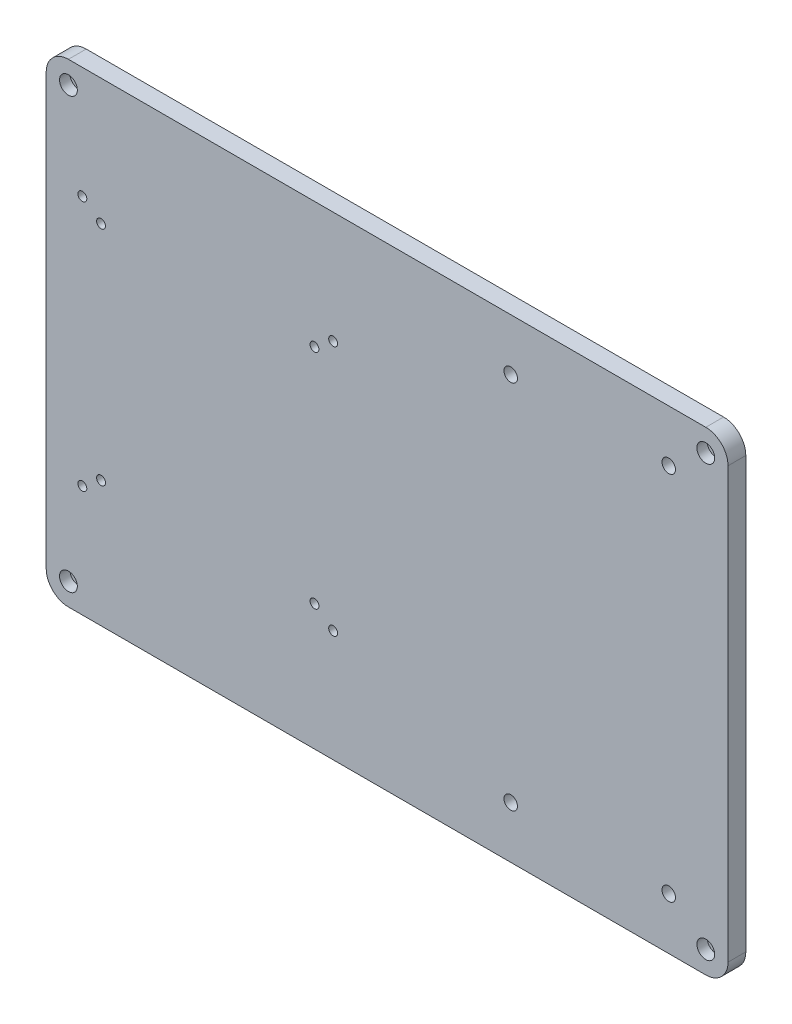
SolidWorks part; units mm, degrees
ref_plane "Front Plane" through (0, 0, 0) normal (0, 0, 1) x (1, 0, 0)
ref_plane "Top Plane" through (0, 0, 0) normal (0, 1, 0) x (1, 0, 0)
ref_plane "Right Plane" through (0, 0, 0) normal (1, 0, 0) x (0, 0, -1)
sketch "Sketch1" plane through (0, 0, 0) normal (0, 0, 1) x (1, 0, 0)
  line L1 (-107.5, 80) -> (107.5, 80)
  line L2 (-115, 72.5) -> (-115, -72.5)
  line L3 (-107.5, -80) -> (107.5, -80)
  line L4 (115, 72.5) -> (115, -72.5)
  line L5 (-115, 80) -> (115, -80) construction
  line L6 (-115, -80) -> (115, 80) construction
  arc A0 (-115, -72.5) -> (-107.5, -80) centre (-107.5, -72.5) ccw
  arc A1 (107.5, -80) -> (115, -72.5) centre (107.5, -72.5) ccw
  arc A2 (107.5, 80) -> (115, 72.5) centre (107.5, 72.5) cw
  arc A3 (-107.5, 80) -> (-115, 72.5) centre (-107.5, 72.5) ccw
  point P0 (0, 0)
  dimension "D3" = 7.5
  dimension "D1" = 230
  dimension "D2" = 160
extrude "Boss-Extrude1" add sketch "Sketch1" along normal blind 6
sketch "Sketch2" plane through (0, 0, 6) normal (0, 0, 1) x (1, 0, 0)
  line L0 (-115, 72.5) -> (-115, -72.5) construction
  line L1 (-107.5, -80) -> (107.5, -80) construction
  line L2 (107.5, 80) -> (-107.5, 80) construction
  line L3 (115, -72.5) -> (115, 72.5) construction
  circle A0 centre (-107.5, -72.5) radius 1.75
  circle A1 centre (-107.5, 72.5) radius 1.75
  circle A2 centre (107.5, -72.5) radius 1.75
  circle A3 centre (107.5, 72.5) radius 1.75
  dimension "D1" = 7.5
  dimension "D3" = 3.5
  dimension "D4" = 3.5
  dimension "D7" = 3.5
  dimension "D10" = 3.5
  dimension "D2" = 7.5
  dimension "D5" = 7.5
  dimension "D6" = 7.5
  dimension "D8" = 7.5
  dimension "D9" = 7.5
  dimension "D11" = 7.5
  dimension "D12" = 7.5
extrude "Cut-Extrude1" cut sketch "Sketch2" against normal blind 10
sketch "Sketch3" plane through (0, 0, 6) normal (0, 0, 1) x (1, 0, 0)
  circle A0 centre (-107.5, -72.5) radius 3
  circle A1 centre (-107.5, 72.5) radius 3
  circle A2 centre (107.5, 72.5) radius 3
  circle A3 centre (107.5, -72.5) radius 3
  dimension "D1" = 6
  dimension "D2" = 6
  dimension "D3" = 6
  dimension "D4" = 6
extrude "Cut-Extrude2" cut sketch "Sketch3" against normal blind 3.5
sketch "Sketch4" plane through (0, 0, 6) normal (0, 0, 1) x (1, 0, 0)
  line L0 (107.5, 80) -> (-107.5, 80) construction
  line L3 (-115, 72.5) -> (-115, -72.5) construction
  line L4 (-107.5, -80) -> (107.5, -80) construction
  circle A0 centre (-96.5, 37.5) radius 1.5
  circle A1 centre (-96.5, -37.5) radius 1.5
  circle A2 centre (-24.5, 37.5) radius 1.5
  circle A3 centre (-24.5, -37.5) radius 1.5
  dimension "D2" = 3
  dimension "D3" = 3
  dimension "D6" = 3
  dimension "D7" = 3
  dimension "D1" = 75
  dimension "D4" = 42.5
  dimension "D5" = 18.5
  dimension "D8" = 72
  dimension "D9" = 72
  dimension "D10" = 42.5
  dimension "D11" = 42.5
extrude "Cut-Extrude3" cut sketch "Sketch4" against normal through all
sketch "Sketch5" plane through (0, 0, 6) normal (0, 0, 1) x (1, 0, 0)
  line L0 (-107.5, -80) -> (107.5, -80) construction
  line L2 (115, -72.5) -> (115, 72.5) construction
  circle A0 centre (95, -62.5) radius 2.2734
  circle A1 centre (95, 62.5) radius 2.2734
  circle A2 centre (41.7, -62.5) radius 2.2734
  circle A3 centre (41.7, 62.5) radius 2.2734
  dimension "D1" = 125
  dimension "D4" = 4.5469
  dimension "D6" = 53.3
  dimension "D2" = 17.5
  dimension "D3" = 20
  dimension "D5" = 53.3
extrude "Cut-Extrude4" cut sketch "Sketch5" against normal through all and the other way through all
sketch "Sketch7" plane through (0, 0, 6) normal (0, 0, 1) x (1, 0, 0)
  circle A0 centre (-102.8, 42.3) radius 1.5
  circle A1 centre (-96.5, 37.5) radius 1.5 construction
  circle A2 centre (-102.8, -42.3) radius 1.5
  circle A3 centre (-18.2, -42.3) radius 1.5
  circle A4 centre (-18.2, 42.3) radius 1.5
  circle A5 centre (-96.5, -37.5) radius 1.5 construction
  circle A6 centre (-24.5, -37.5) radius 1.5 construction
  circle A7 centre (-24.5, 37.5) radius 1.5 construction
  dimension "D1" = 6.3
  dimension "D3" = 3
  dimension "D4" = 3
  dimension "D5" = 3
  dimension "D6" = 3
  dimension "D7" = 4.8
  dimension "D8" = 6.3
  dimension "D10" = 4.8
  dimension "D11" = 4.8
  dimension "D12" = 6.3
  dimension "D2" = 4.8
extrude "Cut-Extrude6" cut sketch "Sketch7" against normal through all
sketch "Sketch8" plane through (0, 0, 0) normal (0, 0, -1) x (-1, 0, 0)
  circle A0 centre (18.2, 42.3) radius 3
  circle A1 centre (18.2, -42.3) radius 3
  circle A2 centre (102.8, -42.3) radius 3
  circle A3 centre (102.8, 42.3) radius 3
  dimension "D1" = 6
  dimension "D2" = 6
  dimension "D3" = 6
  dimension "D4" = 6
extrude "Cut-Extrude7" cut sketch "Sketch8" against normal blind 3.5
